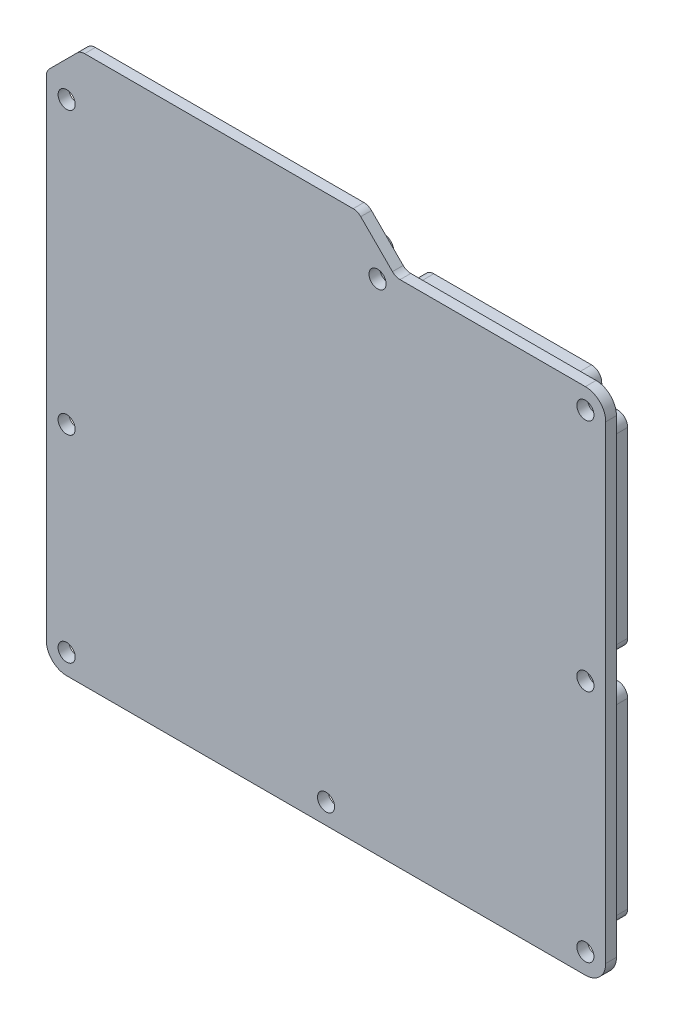
SolidWorks part; units mm, degrees
note: The reader was unsure of these and kept them because the rebuilt part matched: shared geometry of "Sketch1<3>".
ref_plane "Front Plane" through (0, 0, 0) normal (0, 0, 1) x (1, 0, 0)
ref_plane "Top Plane" through (0, 0, 0) normal (0, 1, 0) x (1, 0, 0)
ref_plane "Right Plane" through (0, 0, 0) normal (1, 0, 0) x (0, 0, -1)
sketch "Sketch1" plane through (0, 0, 0) normal (0, 0, 1) x (1, 0, 0)
  line L0 (66.6651, 36.774) -> (37.188, 36.774)
  line L1 (28.1299, 45.774) -> (-22.0432, 45.774)
  line L2 (-20.5549, 38.574) -> (27.8344, 38.574)
  line L3 (-27.3049, 31.824) -> (-27.3049, -11.0347)
  line L4 (-27.3049, -20.7347) -> (-27.3049, -47.916)
  line L5 (-20.5549, -54.666) -> (18.2051, -54.666)
  line L6 (27.9051, -54.666) -> (66.6651, -54.666)
  line L7 (73.4151, -13.796) -> (73.4151, -47.916)
  line L8 (73.4151, 30.024) -> (73.4151, -4.096)
  line L9 (66.6651, 35.424) -> (43.9865, 35.424)
  line L10 (72.0651, 30.024) -> (72.0651, 4.7774)
  line L11 (72.0651, -13.796) -> (72.0651, -47.916)
  line L12 (27.9051, -53.316) -> (42.6365, -53.316)
  line L13 (-20.5549, -53.316) -> (16.4948, -53.316)
  line L14 (-25.9549, -20.7347) -> (-25.9549, -47.916)
  line L15 (-25.9549, 31.824) -> (-25.9549, 4.7774)
  line L16 (66.6651, 36.874) -> (37.188, 36.874)
  line L17 (73.5151, 30.024) -> (73.5151, -4.096)
  line L18 (73.5151, -13.796) -> (73.5151, -47.916)
  line L19 (27.9051, -54.766) -> (66.6651, -54.766)
  line L20 (-20.5549, -54.766) -> (18.2051, -54.766)
  line L21 (-27.4049, -20.7347) -> (-27.4049, -47.916)
  line L22 (-27.4049, 31.824) -> (-27.4049, -11.0347)
  line L23 (-20.5549, 38.674) -> (27.8344, 38.674)
  line L24 (75.3151, -52.766) -> (75.3151, 34.874)
  line L25 (71.5151, 38.674) -> (36.8868, 38.674)
  line L26 (35.4726, 39.2598) -> (29.5442, 45.1882)
  line L27 (-23.4574, 45.1882) -> (-28.6191, 40.0265)
  line L28 (-29.2049, 38.6123) -> (-29.2049, -52.766)
  line L29 (-25.4049, -56.566) -> (71.5151, -56.566)
  line L30 (-20.5549, 37.224) -> (16.4948, 37.224)
  line L31 (42.6365, 35.424) -> (42.6365, 4.7774)
  line L32 (43.9865, 35.424) -> (43.9865, 4.7774)
  line L33 (16.4948, 37.224) -> (16.4948, 4.7774)
  line L34 (17.8448, 37.224) -> (17.8448, 4.7774)
  line L35 (-25.9549, 3.4274) -> (16.4948, 3.4274)
  line L36 (-25.9549, 4.7774) -> (16.4948, 4.7774)
  line L37 (17.8448, -53.316) -> (18.2051, -53.316)
  line L38 (43.9865, -53.316) -> (66.6651, -53.316)
  line L39 (-20.5549, -53.316) -> (18.2051, -53.316) construction
  line L40 (42.6365, 35.424) -> (37.188, 35.424)
  line L41 (27.9051, -53.316) -> (66.6651, -53.316) construction
  line L42 (72.0651, 3.4274) -> (72.0651, -4.096)
  line L43 (66.6651, 35.424) -> (37.188, 35.424) construction
  line L44 (42.6365, 3.4274) -> (42.6365, -53.316)
  line L45 (72.0651, 30.024) -> (72.0651, -4.096) construction
  line L46 (43.9865, 3.4274) -> (72.0651, 3.4274)
  line L47 (42.6365, 35.424) -> (42.6365, -53.316) construction
  line L48 (43.9865, 3.4274) -> (43.9865, -53.316)
  line L49 (-25.9549, 3.4274) -> (72.0651, 3.4274) construction
  line L50 (43.9865, 4.7774) -> (72.0651, 4.7774)
  line L51 (43.9865, 35.424) -> (43.9865, -53.316) construction
  line L52 (-25.9549, 3.4274) -> (-25.9549, -11.0347)
  line L53 (-25.9549, 4.7774) -> (72.0651, 4.7774) construction
  line L54 (16.4948, 3.4274) -> (16.4948, -53.316)
  line L55 (-25.9549, 31.824) -> (-25.9549, -11.0347) construction
  line L56 (17.8448, 3.4274) -> (42.6365, 3.4274)
  line L57 (16.4948, 37.224) -> (16.4948, -53.316) construction
  line L58 (17.8448, 3.4274) -> (17.8448, -53.316)
  line L59 (17.8448, 4.7774) -> (42.6365, 4.7774)
  line L60 (17.8448, 37.224) -> (17.8448, -53.316) construction
  line L61 (17.8448, 37.224) -> (27.8344, 37.224)
  line L63 (-20.5549, 37.224) -> (27.8344, 37.224) construction
  circle A0 centre (-25.4049, 36.674) radius 1.6
  circle A1 centre (-25.4049, -15.8847) radius 1.6
  circle A2 centre (-25.4049, -52.766) radius 1.6
  circle A3 centre (23.0551, -52.766) radius 1.6
  circle A4 centre (32.6844, 36.674) radius 1.6
  circle A5 centre (71.5151, 34.874) radius 1.6
  circle A6 centre (71.5151, -8.946) radius 1.6
  circle A7 centre (71.5151, -52.766) radius 1.6
  arc A8 (37.188, 36.774) -> (35.4237, 35.5791) centre (37.188, 34.874) ccw
  arc A9 (29.7344, 36.674) -> (35.4237, 35.5791) centre (32.6844, 36.674) ccw
  arc A10 (29.7344, 36.674) -> (27.8344, 38.574) centre (27.8344, 36.674) ccw
  arc A11 (-20.5549, 38.574) -> (-22.4549, 36.674) centre (-20.5549, 36.674) ccw
  arc A12 (-25.4049, 33.724) -> (-22.4549, 36.674) centre (-25.4049, 36.674) ccw
  arc A13 (-25.4049, 33.724) -> (-27.3049, 31.824) centre (-25.4049, 31.824) ccw
  arc A14 (-27.3049, -11.0347) -> (-25.4049, -12.9347) centre (-25.4049, -11.0347) ccw
  arc A15 (-25.4049, -18.8347) -> (-25.4049, -12.9347) centre (-25.4049, -15.8847) ccw
  arc A16 (-25.4049, -18.8347) -> (-27.3049, -20.7347) centre (-25.4049, -20.7347) ccw
  arc A17 (-27.3049, -47.916) -> (-25.4049, -49.816) centre (-25.4049, -47.916) ccw
  arc A18 (-22.4549, -52.766) -> (-25.4049, -49.816) centre (-25.4049, -52.766) ccw
  arc A19 (-22.4549, -52.766) -> (-20.5549, -54.666) centre (-20.5549, -52.766) ccw
  arc A20 (18.2051, -54.666) -> (20.1051, -52.766) centre (18.2051, -52.766) ccw
  arc A21 (26.0051, -52.766) -> (20.1051, -52.766) centre (23.0551, -52.766) ccw
  arc A22 (26.0051, -52.766) -> (27.9051, -54.666) centre (27.9051, -52.766) ccw
  arc A23 (66.6651, -54.666) -> (68.5651, -52.766) centre (66.6651, -52.766) ccw
  arc A24 (71.5151, -49.816) -> (68.5651, -52.766) centre (71.5151, -52.766) ccw
  arc A25 (71.5151, -49.816) -> (73.4151, -47.916) centre (71.5151, -47.916) ccw
  arc A26 (73.4151, -13.796) -> (71.5151, -11.896) centre (71.5151, -13.796) ccw
  arc A27 (71.5151, -5.996) -> (71.5151, -11.896) centre (71.5151, -8.946) ccw
  arc A28 (71.5151, -5.996) -> (73.4151, -4.096) centre (71.5151, -4.096) ccw
  arc A29 (73.4151, 30.024) -> (71.5151, 31.924) centre (71.5151, 30.024) ccw
  arc A30 (68.5651, 34.874) -> (71.5151, 31.924) centre (71.5151, 34.874) ccw
  arc A31 (73.5151, 30.024) -> (71.5151, 32.024) centre (71.5151, 30.024) ccw
  arc A32 (68.6651, 34.874) -> (71.5151, 32.024) centre (71.5151, 34.874) ccw
  arc A33 (68.6651, 34.874) -> (66.6651, 36.874) centre (66.6651, 34.874) ccw
  arc A34 (37.188, 36.874) -> (35.3308, 35.6162) centre (37.188, 34.874) ccw
  arc A35 (29.8344, 36.674) -> (35.3308, 35.6162) centre (32.6844, 36.674) ccw
  arc A36 (29.8344, 36.674) -> (27.8344, 38.674) centre (27.8344, 36.674) ccw
  arc A37 (71.5151, -6.096) -> (73.5151, -4.096) centre (71.5151, -4.096) ccw
  arc A38 (71.5151, -6.096) -> (71.5151, -11.796) centre (71.5151, -8.946) ccw
  arc A39 (73.5151, -13.796) -> (71.5151, -11.796) centre (71.5151, -13.796) ccw
  arc A40 (71.5151, -49.916) -> (73.5151, -47.916) centre (71.5151, -47.916) ccw
  arc A41 (71.5151, -49.916) -> (68.6651, -52.766) centre (71.5151, -52.766) ccw
  arc A42 (66.6651, -54.766) -> (68.6651, -52.766) centre (66.6651, -52.766) ccw
  arc A43 (25.9051, -52.766) -> (27.9051, -54.766) centre (27.9051, -52.766) ccw
  arc A44 (25.9051, -52.766) -> (20.2051, -52.766) centre (23.0551, -52.766) ccw
  arc A45 (18.2051, -54.766) -> (20.2051, -52.766) centre (18.2051, -52.766) ccw
  arc A46 (-22.5549, -52.766) -> (-20.5549, -54.766) centre (-20.5549, -52.766) ccw
  arc A47 (-22.5549, -52.766) -> (-25.4049, -49.916) centre (-25.4049, -52.766) ccw
  arc A48 (-27.4049, -47.916) -> (-25.4049, -49.916) centre (-25.4049, -47.916) ccw
  arc A49 (-25.4049, -18.7347) -> (-27.4049, -20.7347) centre (-25.4049, -20.7347) ccw
  arc A50 (-25.4049, -18.7347) -> (-25.4049, -13.0347) centre (-25.4049, -15.8847) ccw
  arc A51 (-27.4049, -11.0347) -> (-25.4049, -13.0347) centre (-25.4049, -11.0347) ccw
  arc A52 (-25.4049, 33.824) -> (-27.4049, 31.824) centre (-25.4049, 31.824) ccw
  arc A53 (-25.4049, 33.824) -> (-22.5549, 36.674) centre (-25.4049, 36.674) ccw
  arc A54 (-20.5549, 38.674) -> (-22.5549, 36.674) centre (-20.5549, 36.674) ccw
  arc A55 (71.5151, -56.566) -> (75.3151, -52.766) centre (71.5151, -52.766) ccw
  arc A56 (75.3151, 34.874) -> (71.5151, 38.674) centre (71.5151, 34.874) ccw
  arc A57 (35.4726, 39.2598) -> (36.8868, 38.674) centre (36.8868, 40.674) ccw
  arc A58 (29.5442, 45.1882) -> (28.1299, 45.774) centre (28.1299, 43.774) ccw
  arc A59 (-22.0432, 45.774) -> (-23.4574, 45.1882) centre (-22.0432, 43.774) ccw
  arc A60 (-28.6191, 40.0265) -> (-29.2049, 38.6123) centre (-27.2049, 38.6123) ccw
  arc A61 (-29.2049, -52.766) -> (-25.4049, -56.566) centre (-25.4049, -52.766) ccw
  arc A62 (68.5651, 34.874) -> (66.6651, 36.774) centre (66.6651, 34.874) ccw
  arc A63 (28.3844, 36.674) -> (36.6772, 35.0781) centre (32.6844, 36.674) ccw
  arc A64 (37.188, 35.424) -> (36.6772, 35.0781) centre (37.188, 34.874) ccw
  arc A65 (67.2151, 34.874) -> (66.6651, 35.424) centre (66.6651, 34.874) ccw
  arc A66 (67.2151, 34.874) -> (71.5151, 30.574) centre (71.5151, 34.874) ccw
  arc A67 (72.0651, 30.024) -> (71.5151, 30.574) centre (71.5151, 30.024) ccw
  arc A68 (71.5151, -4.646) -> (72.0651, -4.096) centre (71.5151, -4.096) ccw
  arc A69 (71.5151, -4.646) -> (71.5151, -13.246) centre (71.5151, -8.946) ccw
  circle A70 centre (-25.4049, -15.8847) radius 1.5 construction
  circle A71 centre (-25.4049, -52.766) radius 1.5 construction
  circle A72 centre (23.0551, -52.766) radius 1.5 construction
  circle A73 centre (71.5151, -52.766) radius 1.5 construction
  circle A74 centre (71.5151, -8.946) radius 1.5 construction
  circle A75 centre (71.5151, 34.874) radius 1.5 construction
  circle A76 centre (32.6844, 36.674) radius 1.5 construction
  circle A77 centre (-25.4049, 36.674) radius 1.5 construction
  arc A78 (72.0651, -13.796) -> (71.5151, -13.246) centre (71.5151, -13.796) ccw
  arc A79 (71.5151, -48.466) -> (72.0651, -47.916) centre (71.5151, -47.916) ccw
  arc A80 (71.5151, -48.466) -> (67.2151, -52.766) centre (71.5151, -52.766) ccw
  arc A81 (66.6651, -53.316) -> (67.2151, -52.766) centre (66.6651, -52.766) ccw
  arc A82 (27.3551, -52.766) -> (27.9051, -53.316) centre (27.9051, -52.766) ccw
  arc A83 (27.3551, -52.766) -> (18.7551, -52.766) centre (23.0551, -52.766) ccw
  arc A84 (18.2051, -53.316) -> (18.7551, -52.766) centre (18.2051, -52.766) ccw
  arc A85 (-21.1049, -52.766) -> (-20.5549, -53.316) centre (-20.5549, -52.766) ccw
  arc A86 (-21.1049, -52.766) -> (-25.4049, -48.466) centre (-25.4049, -52.766) ccw
  arc A87 (-25.9549, -47.916) -> (-25.4049, -48.466) centre (-25.4049, -47.916) ccw
  arc A88 (-25.4049, -20.1847) -> (-25.9549, -20.7347) centre (-25.4049, -20.7347) ccw
  arc A89 (-25.4049, -20.1847) -> (-25.4049, -11.5847) centre (-25.4049, -15.8847) ccw
  arc A90 (-25.9549, -11.0347) -> (-25.4049, -11.5847) centre (-25.4049, -11.0347) ccw
  arc A91 (-25.4049, 32.374) -> (-25.9549, 31.824) centre (-25.4049, 31.824) ccw
  arc A92 (-25.4049, 32.374) -> (-21.1049, 36.674) centre (-25.4049, 36.674) ccw
  arc A93 (-20.5549, 37.224) -> (-21.1049, 36.674) centre (-20.5549, 36.674) ccw
  arc A94 (28.3844, 36.674) -> (27.8344, 37.224) centre (27.8344, 36.674) ccw
  dimension "D1" = 0.1
  dimension "D2" = 0.1
  dimension "D3" = 1.35
  dimension "D4" = 1.35
  dimension "D5" = 1.35
  dimension "D6" = 1.35
extrude "Boss-Extrude1" add sketch "Sketch1" against normal blind 4 contours A30 A62 L0 A8 A9 A10 L2 A11 A12 A13 L3 A14 A15 A16 L4 A17 A18 A19 L5 A20 A21 A22 L6 A23 A24 A25 L7 A26 A27 A28 L8 A29 A94 A63 A64 L40 L31 L59 L34 L61 A93 L30 L33 L36 L15 A91 A92 A90 | L29 A55 L24 A56 L25 A57 L26 A58 L1 A59 L27 A60 L28 A61
extrude "Boss-Extrude2" add sketch "Sketch1<3>" along normal blind 2 contours L28 A61 L29 A55 L24 A56 L25 A57 L26 A58 L1 A59 L27 A60 A0 A1 A2 A3 A4 A5 A6 A7 A54 L23 A36 A35 A34 L16 A33 A32 A31 L17 A37 A38 A39 L18 A40 A41 A42 L19 A43 A44 | A30 A62 L0 A8 A9 A10 L2 A11 A12 A13 L3 A14 A15 A16 L4 A17 A18 A19 L5 A20 A21 A22 L6 A23 A24 A25 L7 A26 A27 A28 L8 A29 A94 A63 A64 L40 L31 L59 L34 L61 A93 L30 L33 L36 L15 A91 A92 A90 | L23 A54 A53 A52 L22 A51 A50 A49 L21 A48 A47 A46 L20 A45 A44 A43 L19 A42 A41 A40 L18 A39 A38 A37 L17 A31 A32 A33 L16 A34 A35 A36 A62 A30 A29 L8 A28 A27 A26 L7 A25 A24 A23 L6 A22 A21 A20 L5 A19 A18 | L38 A81 A80 A79 L11 A78 A69 A68 L42 L46 L48 | L10 A67 A66 A65 L9 L32 L50 | A63 A94 L61 L34 L59 L31 L40 A64 | L37 A84 A83 A82 L12 L44 L56 L58 | L52 A90 A89 A88 L14 A87 A86 A85 L13 L54 L35 | L30 A93 A92 A91 L15 L36 L33
sketch "Sketch1<3>" plane through (0, 0, 0) normal (0, 0, 1) x (1, 0, 0) same geometry as "Sketch1"
